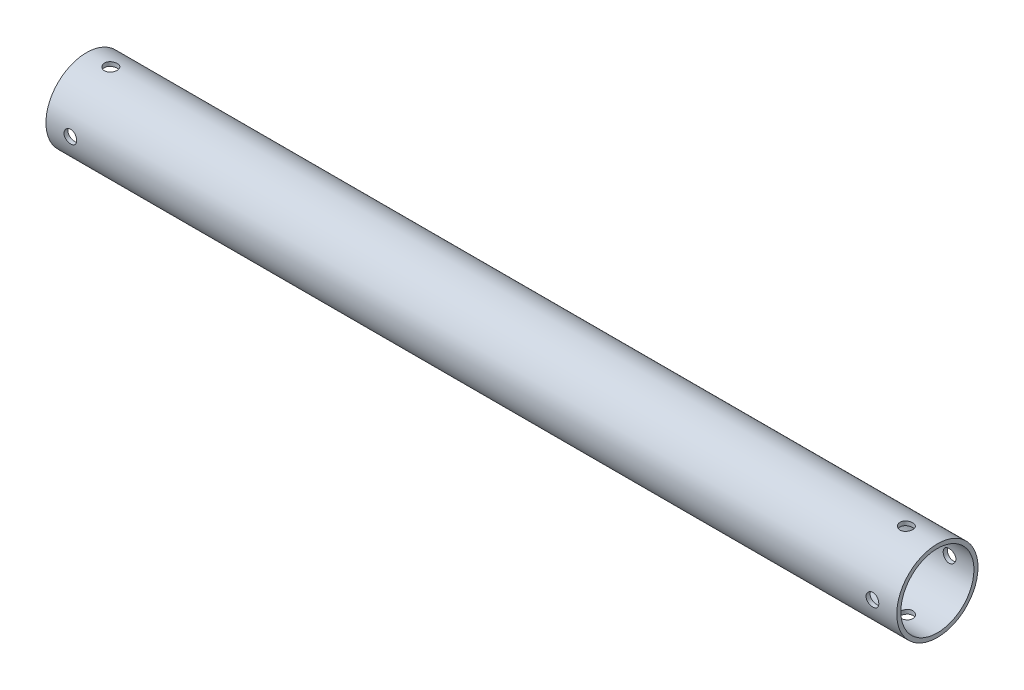
SolidWorks part; units mm, degrees
material "PC High Viscosity"
ref_plane "Front Plane" through (0, 0, 0) normal (0, 0, 1) x (1, 0, 0)
ref_plane "Top Plane" through (0, 0, 0) normal (0, 1, 0) x (1, 0, 0)
ref_plane "Right Plane" through (0, 0, 0) normal (1, 0, 0) x (0, 0, -1)
sketch "Sketch1" plane through (0, 0, 0) normal (1, 0, 0) x (0, 0, -1)
  circle A0 centre (0, 0) radius 15.875
  dimension "D1" = 31.75
extrude "Extrude-Thin1" add sketch "Sketch1" along normal mid plane 332.5813 thin thin type one direction reverse wall 1.5875
sketch "Sketch2" plane through (0, 0, 0) normal (0, 0, 1) x (1, 0, 0)
  line L0 (-166.2906, -15.875) -> (166.2906, -15.875) construction
  line L1 (104.0156, -15.875) -> (125.0156, -15.875)
  line L2 (104.0156, -15.875) -> (104.0156, 15.875)
  line L3 (104.0156, 15.875) -> (125.0156, 15.875)
  line L4 (125.0156, -15.875) -> (125.0156, 15.875)
  line L5 (166.2906, 15.875) -> (-166.2906, 15.875) construction
  line L6 (166.2906, -15.875) -> (166.2906, 15.875) construction
  line L7 (0, 0) -> (0, 11.1276) construction
  line L8 (-125.0156, -15.875) -> (-125.0156, 15.875)
  line L9 (-104.0156, 15.875) -> (-125.0156, 15.875)
  line L10 (-104.0156, -15.875) -> (-104.0156, 15.875)
  line L11 (-104.0156, -15.875) -> (-125.0156, -15.875)
  line L13 (166.2906, -15.875) -> (163.9665, -15.875)
  line L14 (166.2906, -15.875) -> (166.2906, 15.875)
  line L15 (166.2906, 15.875) -> (163.9665, 15.875)
  line L16 (163.9665, -15.875) -> (163.9665, 15.875)
  dimension "D1" = 41.275
  dimension "D2" = 21
  dimension "D3" = 2.3241
sketch "Sketch3" plane through (0, 0, 0) normal (0, 0, 1) x (1, 0, 0)
  line L0 (-166.2906, 15.875) -> (-166.2906, -15.875) construction
  line L1 (166.2906, -15.875) -> (166.2906, 15.875) construction
  circle A0 centre (-156.7656, 0) radius 2.4892
  circle A1 centre (156.7656, 0) radius 2.4892
  dimension "D1" = 4.9784
  dimension "D2" = 9.525
  dimension "D3" = 9.525
extrude "Cut-Extrude1" cut sketch "Sketch3" against normal through all both and the other way through all
sketch "Sketch4" plane through (0, 0, 0) normal (0, 1, 0) x (1, 0, 0)
  line L0 (-166.2906, 15.875) -> (-166.2906, -15.875) construction
  circle A0 centre (154.1883, 0) radius 2.4892
  circle A1 centre (-156.7656, 0) radius 2.4892
  dimension "D1" = 4.9784
  dimension "D2" = 9.525
extrude "Cut-Extrude2" cut sketch "Sketch4" against normal through all both and the other way through all
equation "\"D2@Sketch2\"=21mm"
